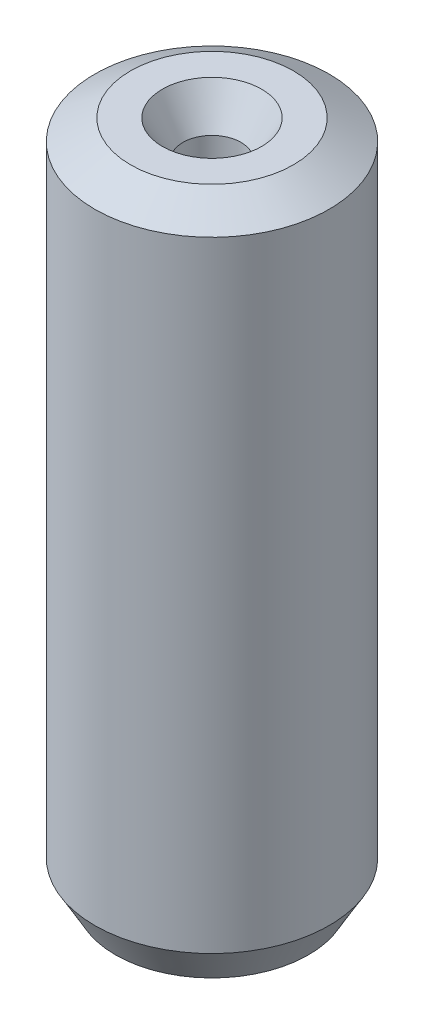
SolidWorks part; units mm, degrees
ref_plane "Front Plane" through (0, 0, 0) normal (0, 0, 1) x (1, 0, 0)
ref_plane "Top Plane" through (0, 0, 0) normal (0, 1, 0) x (1, 0, 0)
ref_plane "Right Plane" through (0, 0, 0) normal (1, 0, 0) x (0, 0, -1)
sketch "Sketch1" plane through (0, 0, 0) normal (0, 1, 0) x (1, 0, 0)
  circle A0 centre (0, 0) radius 5
  dimension "SLEEVE_OD" = 10
extrude "Boss-Extrude1" add sketch "Sketch1" along normal blind 28.8736
sketch "Sketch2" plane through (0, 0, 0) normal (0, 1, 0) x (1, 0, 0)
  circle A0 centre (0, 0) radius 1.2382
  dimension "BORE_D" = 2.4764
extrude "Cut-Extrude1" cut sketch "Sketch2" along normal through all
chamfer "Chamfer1" distance 0.8803 angle 60 4 edges at (0, 28.8736, 1.2382) (0, 0, 1.2382) (0, 0, 5) (0, 28.8736, 5) first distance on face at (0, 28.8736, 1.2382) first distance on face at (0, 0, 1.2382) first distance on face at (0, 28.8736, 5)
